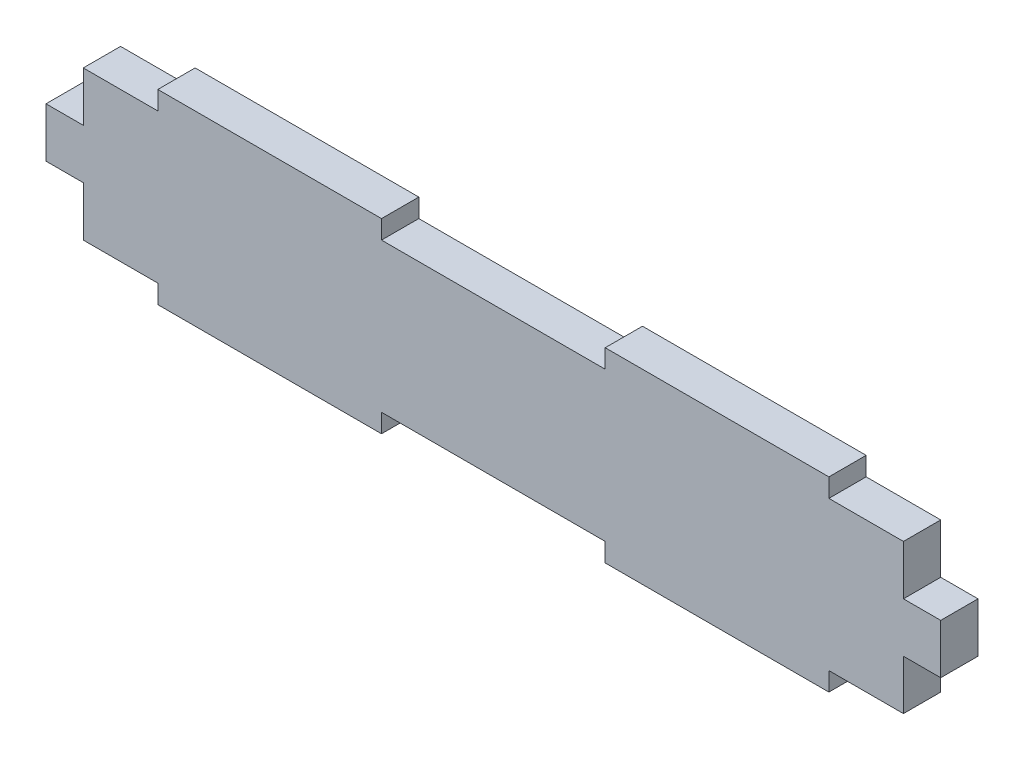
SolidWorks part; units mm, degrees
ref_plane "Front Plane" through (0, 0, 0) normal (0, 0, 1) x (1, 0, 0)
ref_plane "Top Plane" through (0, 0, 0) normal (0, 1, 0) x (1, 0, 0)
ref_plane "Right Plane" through (0, 0, 0) normal (1, 0, 0) x (0, 0, -1)
sketch "Sketch1" plane through (0, 0, 0) normal (0, 0, 1) x (1, 0, 0)
  line L1 (-152.4, -25.4) -> (152.4, -25.4)
  line L2 (-152.4, -25.4) -> (-152.4, 25.4)
  line L3 (-152.4, 25.4) -> (152.4, 25.4)
  line L4 (152.4, -25.4) -> (152.4, 25.4)
  line L5 (-152.4, -25.4) -> (152.4, 25.4) construction
  line L6 (-152.4, 25.4) -> (152.4, -25.4) construction
  point P0 (0, 0)
  dimension "D1" = 304.8
  dimension "D2" = 50.8
extrude "Boss-Extrude1" add sketch "Sketch1" along normal blind 12.7 contours L1 L3 region at (0, 0, 0)
sketch "Sketch2" plane through (0, 0, 12.7) normal (0, 0, 1) x (1, 0, 0)
  line L0 (-152.4, -25.4) -> (152.4, -25.4) construction
  line L1 (-38.1, -25.4) -> (-114.3, -25.4)
  line L2 (-38.1, -25.4) -> (-38.1, -31.75)
  line L3 (-38.1, -31.75) -> (-114.3, -31.75)
  line L4 (-114.3, -25.4) -> (-114.3, -31.75)
  line L5 (0, -6.985) -> (0, 6.985) construction
  line L6 (38.1, -31.75) -> (114.3, -31.75)
  line L7 (114.3, -25.4) -> (114.3, -31.75)
  line L8 (38.1, -25.4) -> (114.3, -25.4)
  line L9 (38.1, -25.4) -> (38.1, -31.75)
  line L10 (6.985, 0) -> (-6.985, 0) construction
  line L11 (38.1, 25.4) -> (38.1, 31.75)
  line L12 (38.1, 25.4) -> (114.3, 25.4)
  line L13 (114.3, 25.4) -> (114.3, 31.75)
  line L14 (38.1, 31.75) -> (114.3, 31.75)
  line L15 (-38.1, 31.75) -> (-114.3, 31.75)
  line L16 (-114.3, 25.4) -> (-114.3, 31.75)
  line L17 (-38.1, 25.4) -> (-114.3, 25.4)
  line L18 (-38.1, 25.4) -> (-38.1, 31.75)
  point P12 (-38.1, -28.575)
  dimension "D1" = 76.2
  dimension "D2" = 6.35
  dimension "D3" = 76.2
extrude "Boss-Extrude2" add sketch "Sketch2" against normal blind 12.7
sketch "Sketch3" plane through (0, 0, 12.7) normal (0, 0, 1) x (1, 0, 0)
  line L0 (6.985, 0) -> (-6.985, 0) construction
  line L1 (-152.4, -25.4) -> (-139.7, -25.4)
  line L2 (-152.4, -25.4) -> (-152.4, -8.4667)
  line L3 (-152.4, -8.4667) -> (-139.7, -8.4667)
  line L4 (-139.7, -25.4) -> (-139.7, -8.4667)
  line L6 (-152.4, 8.4667) -> (-139.7, 8.4667)
  line L7 (-139.7, 25.4) -> (-139.7, 8.4667)
  line L8 (-152.4, 25.4) -> (-139.7, 25.4)
  line L9 (-152.4, 25.4) -> (-152.4, 8.4667)
  line L10 (0, -6.985) -> (0, 6.985) construction
  line L11 (152.4, 25.4) -> (152.4, 8.4667)
  line L12 (152.4, 25.4) -> (139.7, 25.4)
  line L13 (139.7, 25.4) -> (139.7, 8.4667)
  line L14 (152.4, 8.4667) -> (139.7, 8.4667)
  line L15 (152.4, -8.4667) -> (139.7, -8.4667)
  line L16 (139.7, -25.4) -> (139.7, -8.4667)
  line L17 (152.4, -25.4) -> (139.7, -25.4)
  line L18 (152.4, -25.4) -> (152.4, -8.4667)
  dimension "D1" = 16.9333
  dimension "D2" = 12.7
extrude "Cut-Extrude1" cut sketch "Sketch3" against normal through all
